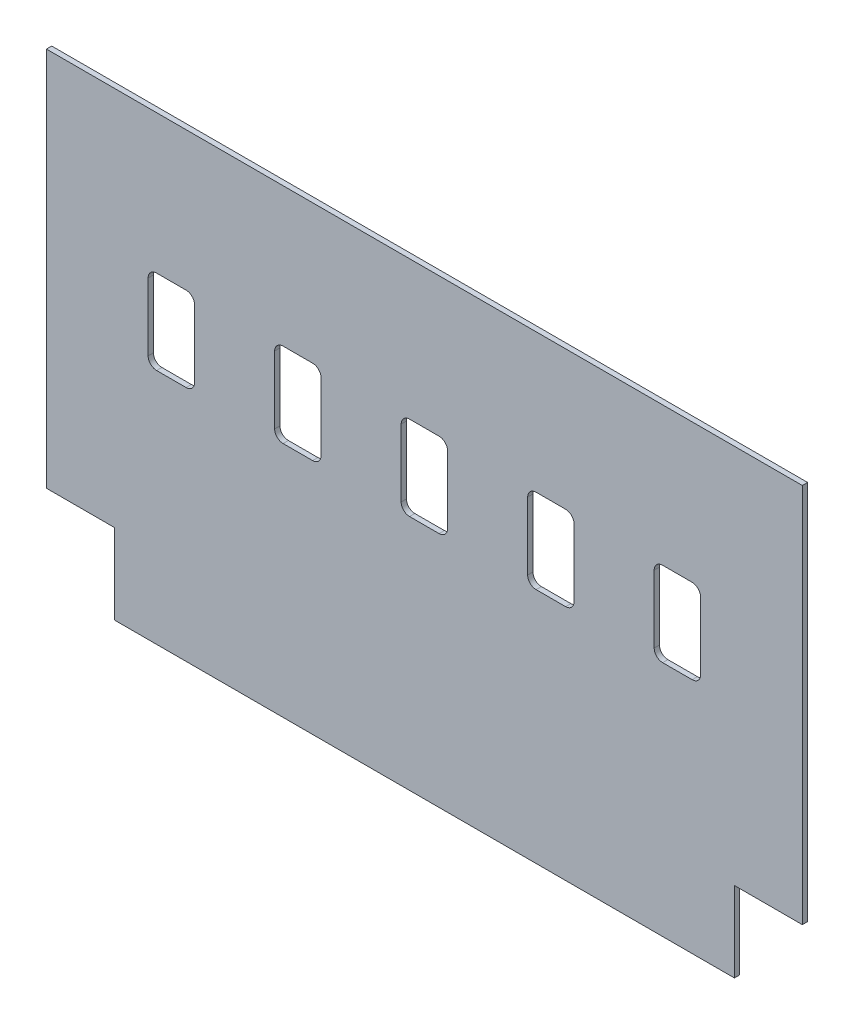
SolidWorks part; units mm, degrees
material "ABS PC"
ref_plane "Front Plane" through (0, 0, 0) normal (0, 0, 1) x (1, 0, 0)
ref_plane "Top Plane" through (0, 0, 0) normal (0, 1, 0) x (1, 0, 0)
ref_plane "Right Plane" through (0, 0, 0) normal (1, 0, 0) x (0, 0, -1)
sketch "Sketch1" plane through (0, 0, 0) normal (0, 0, 1) x (1, 0, 0)
  line L1 (-227.6475, -138.684) -> (227.6475, -138.684)
  line L2 (-227.6475, -138.684) -> (-227.6475, 138.684)
  line L3 (-227.6475, 138.684) -> (227.6475, 138.684)
  line L4 (227.6475, -138.684) -> (227.6475, 138.684)
  line L5 (0, 138.684) -> (0, -138.684) construction
  line L6 (-227.6475, 0) -> (227.6475, 0) construction
  point P0 (0, 0)
  point P4 (-159.0675, 0)
  point P5 (159.0675, 0)
  point P6 (0, 97.0788)
  point P7 (0, -97.0788)
  dimension "Width" = 277.368
  dimension "Break" = 68.58
  dimension "D2" = 68.58
  dimension "D1" = 41.6052
  dimension "D3" = 41.6052
  dimension "D4" = 455.295
sketch "Sketch2" plane through (0, 0, 0) normal (1, 0, 0) x (0, 0, -1)
  line L0 (-1.5875, -138.684) -> (1.5875, -138.684)
  dimension "Thickness" = 3.175
sketch "Sketch3" plane through (0, 0, 0) normal (0, 0, 1) x (1, 0, 0)
  line L0 (-227.6475, -138.684) -> (-227.6475, 138.684) construction
  line L1 (-227.6475, -138.684) -> (227.6475, -138.684) construction
  line L2 (227.6475, -138.684) -> (227.6475, 138.684) construction
  line L3 (-227.6475, 138.684) -> (227.6475, 138.684) construction
  line L4 (-227.6475, -138.684) -> (-227.6475, 138.684)
  line L5 (-227.6475, -138.684) -> (227.6475, -138.684)
  line L6 (227.6475, -138.684) -> (227.6475, 138.684)
  line L7 (-227.6475, 138.684) -> (227.6475, 138.684)
extrude "Boss-Extrude1" add sketch "Sketch3" along normal mid plane 3.175
sketch "Sketch4" plane through (0, 0, 1.5875) normal (0, 0, 1) x (1, 0, 0)
  line L0 (-227.6475, 29.591) -> (-158.75, 29.591) construction
  line L1 (-82.55, 29.591) -> (-82.55, 54.991) construction
  line L2 (-82.55, 54.991) -> (-90.17, 54.991) construction
  line L3 (-158.75, 29.591) -> (-158.75, 54.991) construction
  line L8 (-158.75, 29.591) -> (-82.55, 29.591) construction
  line L9 (-82.55, 29.591) -> (-6.35, 29.591) construction
  line L10 (-6.35, 29.591) -> (69.85, 29.591) construction
  line L11 (69.85, 29.591) -> (146.05, 29.591) construction
  line L12 (-82.55, 29.591) -> (-82.55, 4.191) construction
  line L13 (-82.55, 4.191) -> (-62.23, 4.191) construction
  line L16 (-158.75, 54.991) -> (-166.37, 54.991) construction
  line L17 (-158.75, 29.591) -> (-158.75, 4.191) construction
  line L18 (-158.75, 4.191) -> (-138.43, 4.191) construction
  line L19 (-6.35, 29.591) -> (-6.35, 54.991) construction
  line L20 (-161.29, 54.991) -> (-143.51, 54.991)
  line L21 (-166.37, 49.911) -> (-166.37, 9.271)
  line L22 (-161.29, 4.191) -> (-143.51, 4.191)
  line L23 (-138.43, 49.911) -> (-138.43, 9.271)
  line L24 (-6.35, 54.991) -> (-13.97, 54.991) construction
  line L25 (-6.35, 29.591) -> (-6.35, 4.191) construction
  line L26 (-6.35, 4.191) -> (13.97, 4.191) construction
  line L27 (69.85, 29.591) -> (69.85, 54.991) construction
  line L28 (-8.89, 54.991) -> (8.89, 54.991)
  line L29 (-13.97, 49.911) -> (-13.97, 9.271)
  line L30 (-8.89, 4.191) -> (8.89, 4.191)
  line L31 (13.97, 49.911) -> (13.97, 9.271)
  line L32 (69.85, 54.991) -> (62.23, 54.991) construction
  line L33 (69.85, 29.591) -> (69.85, 4.191) construction
  line L34 (69.85, 4.191) -> (90.17, 4.191) construction
  line L35 (146.05, 29.591) -> (146.05, 54.991) construction
  line L36 (67.31, 54.991) -> (85.09, 54.991)
  line L37 (62.23, 49.911) -> (62.23, 9.271)
  line L38 (67.31, 4.191) -> (85.09, 4.191)
  line L39 (90.17, 49.911) -> (90.17, 9.271)
  line L40 (146.05, 54.991) -> (138.43, 54.991) construction
  line L41 (146.05, 29.591) -> (146.05, 4.191) construction
  line L42 (146.05, 4.191) -> (166.37, 4.191) construction
  line L44 (143.51, 54.991) -> (161.29, 54.991)
  line L45 (138.43, 49.911) -> (138.43, 9.271)
  line L46 (143.51, 4.191) -> (161.29, 4.191)
  line L47 (166.37, 49.911) -> (166.37, 9.271)
  line L48 (-85.09, 54.991) -> (-67.31, 54.991)
  line L49 (-90.17, 49.911) -> (-90.17, 9.271)
  line L50 (-85.09, 4.191) -> (-67.31, 4.191)
  line L51 (-62.23, 49.911) -> (-62.23, 9.271)
  arc A0 (138.43, 9.271) -> (143.51, 4.191) centre (143.51, 9.271) ccw
  arc A1 (166.37, 9.271) -> (161.29, 4.191) centre (161.29, 9.271) cw
  arc A2 (161.29, 54.991) -> (166.37, 49.911) centre (161.29, 49.911) cw
  arc A3 (138.43, 49.911) -> (143.51, 54.991) centre (143.51, 49.911) cw
  arc A4 (62.23, 9.271) -> (67.31, 4.191) centre (67.31, 9.271) ccw
  arc A5 (90.17, 9.271) -> (85.09, 4.191) centre (85.09, 9.271) cw
  arc A6 (85.09, 54.991) -> (90.17, 49.911) centre (85.09, 49.911) cw
  arc A7 (67.31, 54.991) -> (62.23, 49.911) centre (67.31, 49.911) ccw
  arc A8 (-13.97, 9.271) -> (-8.89, 4.191) centre (-8.89, 9.271) ccw
  arc A9 (13.97, 9.271) -> (8.89, 4.191) centre (8.89, 9.271) cw
  arc A10 (8.89, 54.991) -> (13.97, 49.911) centre (8.89, 49.911) cw
  arc A11 (-8.89, 54.991) -> (-13.97, 49.911) centre (-8.89, 49.911) ccw
  arc A15 (-138.43, 9.271) -> (-143.51, 4.191) centre (-143.51, 9.271) cw
  arc A16 (-143.51, 54.991) -> (-138.43, 49.911) centre (-143.51, 49.911) cw
  arc A17 (-166.37, 49.911) -> (-161.29, 54.991) centre (-161.29, 49.911) cw
  arc A18 (-166.37, 9.271) -> (-161.29, 4.191) centre (-161.29, 9.271) ccw
  arc A19 (-90.17, 9.271) -> (-85.09, 4.191) centre (-85.09, 9.271) ccw
  arc A20 (-62.23, 9.271) -> (-67.31, 4.191) centre (-67.31, 9.271) cw
  arc A21 (-67.31, 54.991) -> (-62.23, 49.911) centre (-67.31, 49.911) cw
  arc A22 (-85.09, 54.991) -> (-90.17, 49.911) centre (-85.09, 49.911) ccw
  point P14 (-152.4, 54.991)
  point P15 (-227.6475, 29.591)
  point P16 (-76.2, 54.991)
  point P17 (-90.17, 29.591)
  point P18 (-13.97, 29.591)
  point P95 (62.23, 29.591)
  point P96 (138.43, 29.591)
  point P97 (0, 54.991)
  point P98 (76.2, 54.991)
  point P99 (152.4, 54.991)
  dimension "D1" = 5.08
  dimension "D2" = 5.08
  dimension "D8" = 27.94
  dimension "D9" = 27.94
  dimension "D10" = 27.94
  dimension "D11" = 27.94
  dimension "D12" = 27.94
  dimension "D3" = 76.2
  dimension "D4" = 76.2
  dimension "D5" = 152.4
  dimension "D6" = 152.4
  dimension "D13" = 25.4
  dimension "D14" = 25.4
extrude "Cut-Extrude1" cut sketch "Sketch4" against normal blind 25.4 contours L21 A18 L22 A15 L23 A16 L20 A17 | A22 L48 A21 L51 A20 L50 A19 L49 | L29 A8 L30 A9 L31 A10 L28 A11 | L37 A4 L38 A5 L39 A6 L36 A7 | A3 L44 A2 L47 A1 L46 A0 L45
ref_plane "Plane1" through (224.4725, -107.7083, -4.7625) normal (-1, 0, 0) x (0, 0, 1)
sketch "Sketch8" plane through (0, 0, 1.5875) normal (0, 0, 1) x (1, 0, 0)
  line L0 (0, -1.7463) -> (0, 1.7463) construction
  line L3 (-227.6475, -90.424) -> (-186.7535, -90.424)
  line L4 (-186.7535, -90.424) -> (-186.7535, -138.684)
  line L5 (-227.6475, -90.424) -> (-227.6475, -138.684)
  line L6 (227.6475, -90.424) -> (186.7535, -90.424)
  line L7 (227.6475, -138.684) -> (227.6475, 138.684) construction
  line L8 (186.7535, -90.424) -> (186.7535, -138.684)
  line L9 (-227.6475, -138.684) -> (227.6475, -138.684) construction
  line L10 (-227.6475, -138.684) -> (-186.7535, -138.684)
  line L11 (186.7535, -138.684) -> (227.6475, -138.684)
  line L12 (227.6475, -138.684) -> (227.6475, -90.424)
extrude "Cut-Extrude2" cut sketch "Sketch8" against normal blind 25.4
equation "\"D1@Boss-Extrude1\" = \"Thickness@Sketch2\""
equation "\"D2@Sketch1\" = \"Break@Sketch1\""
equation "\"D1@Sketch1\"=\"Width@Sketch1\"*0.15"
equation "\"D3@Sketch1\"=\"D1@Sketch1\""
equation "\"SlotWidth\"= 1.1in"
equation "\"D8@Sketch4\"=\"SlotWidth\""
equation "\"D9@Sketch4\"=\"SlotWidth\""
equation "\"D10@Sketch4\"=\"SlotWidth\""
equation "\"D11@Sketch4\"=\"SlotWidth\""
equation "\"D12@Sketch4\"=\"SlotWidth\""
